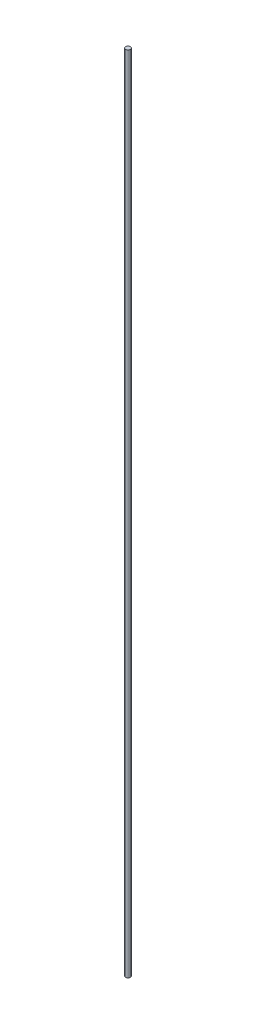
SolidWorks part; units mm, degrees
ref_plane "Спереди" through (0, 0, 0) normal (0, 0, 1) x (1, 0, 0)
ref_plane "Сверху" through (0, 0, 0) normal (0, 1, 0) x (1, 0, 0)
ref_plane "Справа" through (0, 0, 0) normal (1, 0, 0) x (0, 0, -1)
sketch "Эскиз2" plane through (0, 0, 0) normal (0, 0, 1) x (1, 0, 0)
  line L0 (0, 340.6494) -> (-5, 340.6494) construction
  line L5 (-2.5, 340.6494) -> (0, 340.6494)
  line L6 (-2.5, 340.6494) -> (-2.5, -490.6006)
  line L7 (-2.5, -490.6006) -> (0, -490.6006)
  line L8 (0, 340.6494) -> (0, -490.6006)
  line L9 (-2.5, 340.6494) -> (0, -490.6006) construction
  line L10 (-2.5, -490.6006) -> (0, 340.6494) construction
  line L13 (370.4073, -490.6006) -> (-30.7089, -490.6006) construction
  point P0 (-1.25, -74.9756)
  point P12 (0, 0)
  dimension "D1" = 2.5
revolve "Повернуть1" add sketch "Эскиз2" angle 360 about L6
equation "\"Ширина груза\"= 420"
equation "\"Глубина груза\"= 490"
equation "\"Высота груза\"= 297"
equation "\"Ширина ячейки\"= \"Ширина груза\" + 10"
equation "\"Глубина ячейки\"= \"Глубина груза\" + 10"
equation "\"Высота ячейки\"= \"Высота груза\" + 10 + 13"
equation "\"Колво ячеек ширина\"= 2"
equation "\"Колво ячеек высота\"= 2"
equation "\"Толщина стенки\"= 10"
equation "\"Крепление дверцы\"= 5"
equation "\"Ширина рейки\"= \"Толщина шестерни\""
equation "\"Высота рейки\"= 20"
equation "\"Высота пола\"= 20"
equation "\"Колво полозьев\"= 5"
equation "\"Отступ рейки\"= 20"
equation "\"Глубина каретки\"= \"Глубина ячейки\" + 30 + \"Мотор Y высота корпуса\" + 20"
equation "\"Длинна рейки\"= ( \"Ширина ячейки\" + \"Толщина стенки\" + \"Крепление дверцы\" ) * \"Колво ячеек ширина\" + \"Ширина ячейки выгрузки\" * \"Колво выгрузки\" + \"Толщина стенки\""
equation "\"Отступ шпильки\"= 20"
equation "\"Диаметр шпильки\"= 5"
equation "\"Длинна шпильки\"= ( \"Высота ячейки\" + \"Толщина стенки\" + \"Высота пола\" ) * \"Колво ячеек высота\" + ( \"Толщина стенки\" + \"Отступ рейки\" ) * 2 "
equation "\"D1@Эскиз2\"= \"Диаметр шпильки\" / 2"
equation "\"Ширина пластины\"= 50  "
equation "\"Высота зона выгрузки\"= \"Высота ячейки\" * 2 + \"Толщина стенки\" * 2"
equation "\"Колво выгрузки\"= 1"
equation "\"Отступ крепления мотора фиксации\" = 30"
equation "\"Мотор X ширина корпуса\"= 42.3"
equation "\"Мотор X высота корпуса\"= 42.3"
equation "\"Мотор X длина корпуса\"= 40"
equation "\"Мотор X вылет вала\"= 19.8"
equation "\"Мотор Y ширина корпуса\"= 42.3"
equation "\"Мотор Y высота корпуса\"= 42.3"
equation "\"Мотор Y длина корпуса\"= 48"
equation "\"Мотор Y вылет вала\"= 30"
equation "\"Мотор Z ширина корпуса\"= 42"
equation "\"Мотор Z высота корпуса\"= 42"
equation "\"Мотор Z длина корпуса\"= 40"
equation "\"Мотор Z вылет вала\"= 23"
equation "\"Мотор диаметр вала ПРЕДВ\"= 5"
equation "\"Мотор шаг крепления ПРЕДВ\"= 31"
equation "\"Мотор диаметр отверстий ПРЕДВ\"= 3"
equation "\"Мотор глубина отверстий ПРЕДВ\"= 4.5"
equation "\"Мотор диаметр буртика ПРЕДВ\"= 22"
equation "\"Мотор высота буртика ПРЕДВ\"= 2"
equation "\"Мотор диаметр шкива ПРЕДВ\"= 16"
equation "\"Мотор длина шкива ПРЕДВ\"= 12"
equation "\"Мотор отступ шкива ПРЕДВ\"= 5"
equation "\"Мотор X шаг градусов\"= 1.8"
equation "\"Мотор X ток А\"= 1.5"
equation "\"Мотор X сопротивление Ом\"= 1.3"
equation "\"Мотор X индуктивность мГн\"= 2"
equation "\"Мотор Y шаг градусов\"= 1.8"
equation "\"Мотор Y ток А\"= 2.2"
equation "\"Мотор Y сопротивление Ом\"= 0.9"
equation "\"Мотор Y индуктивность мГн\"= 2"
equation "\"Мотор Z шаг градусов\"= 1.8"
equation "\"Мотор Z ток А\"= 1"
equation "\"Мотор Z сопротивление Ом\"= 4"
equation "\"Мотор Z индуктивность мГн\"= 8"
equation "\"Мотор Y диаметр ротора\"= 25.78"
equation "\"Ширина ячейки выгрузки\"= \"Ширина ячейки\" + \"Толщина стенки\" + \"Отступ крепления мотора фиксации\"*2"
